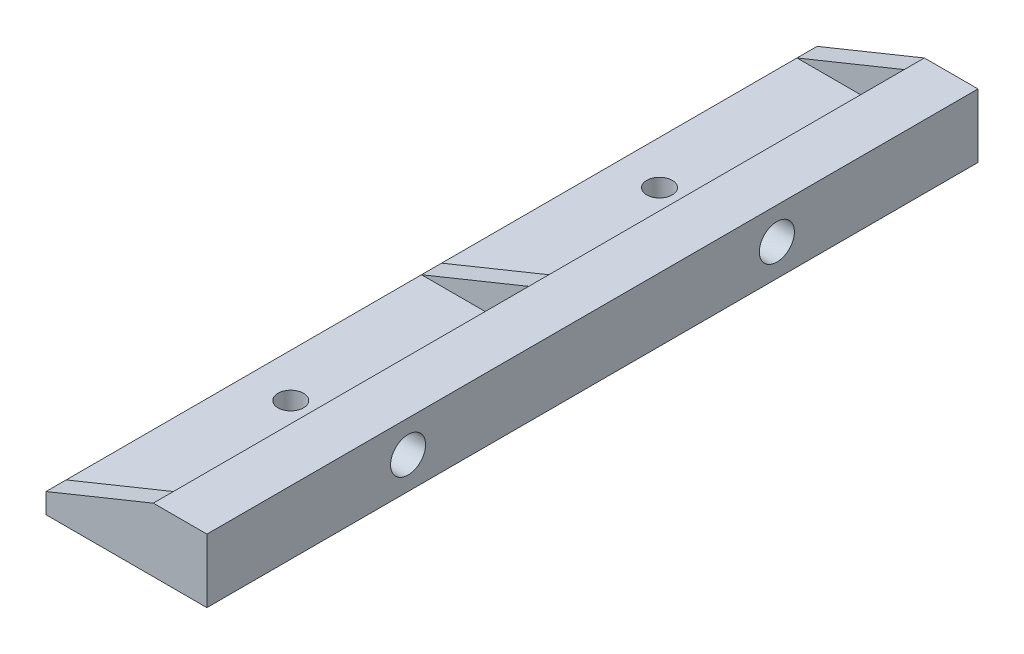
SolidWorks part; units mm, degrees
ref_plane "Front Plane" through (0, 0, 0) normal (0, 0, 1) x (1, 0, 0)
ref_plane "Top Plane" through (0, 0, 0) normal (0, 1, 0) x (1, 0, 0)
ref_plane "Right Plane" through (0, 0, 0) normal (1, 0, 0) x (0, 0, -1)
sketch "Sketch1" plane through (0, 0, 0) normal (0, 0, 1) x (1, 0, 0)
  line L0 (0, 0) -> (0, 9.5)
  line L1 (0, 9.5) -> (-8, 9.5)
  line L2 (-8, 9.5) -> (-8, 6)
  line L3 (-11, 3) -> (-24, 3)
  line L4 (-24, 3) -> (-24, 0)
  line L6 (-24, 0) -> (0, 0)
  arc A0 (-8, 6) -> (-11, 3) centre (-11, 6) cw
  dimension "D1" = 3
  dimension "D2" = 9.5
  dimension "D3" = 24
  dimension "D4" = 8
  dimension "D5" = 3
extrude "Boss-Extrude1" add sketch "Sketch1" along normal blind 115
ref_plane "Plane2" through (0, 0, 0) normal (0, 0, -1) x (-1, 0, 0)
ref_plane "Plane4" through (0, 0, 57.5) normal (0, 0, -1) x (-1, 0, 0)
sketch "Sketch4" plane through (0, 0, 57.5) normal (0, 0, -1) x (-1, 0, 0)
  line L0 (8, 9.5) -> (24, 3)
sketch "Sketch5" plane through (0, 0, 0) normal (0, 0, -1) x (-1, 0, 0)
  line L0 (8, 9.5) -> (24, 3)
rib "Rib3" sketch "Sketch4" sketch "Sketch4" thickness 3 extrusion direction parallel to sketch draft on no parameters "D1"=3
rib "Rib4" sketch "Sketch5" sketch "Sketch5" thickness 3 extrusion direction parallel to sketch draft on no parameters "D1"=3
mirror "Mirror1" about plane through (0, 0, 57.5) normal (0, 0, -1) of "Rib4"
sketch "Sketch6" plane through (0, 0, 0) normal (1, 0, 0) x (0, 0, -1)
  line L0 (-115, 4.75) -> (0, 4.75) construction
  line L1 (-115, 0) -> (-115, 9.5) construction
  line L2 (0, 0) -> (0, 9.5) construction
  circle A0 centre (-85, 4.75) radius 2.3495
  circle A1 centre (-30, 4.75) radius 2.3495
  point P6 (-85, 4.75)
  point P7 (-30, 4.75)
  dimension "D3" = 4.699
  dimension "D1" = 30
  dimension "D2" = 30
sketch "Sketch9" plane through (0, 0, 0) normal (0, -1, 0) x (1, 0, 0)
  line L0 (-17.5, 115) -> (-17.5, 0) construction
  line L1 (-24, 115) -> (0, 115) construction
  line L2 (-24, 0) -> (0, 0) construction
  line L3 (-24, 115) -> (-24, 0) construction
  point P6 (-17.5, 85)
  point P7 (-17.5, 30)
  dimension "D1" = 30
  dimension "D2" = 30
  dimension "D3" = 6.5
hole_wizard "#6 Clearance Hole1" positions "Sketch10" profile "Sketch11" hole size "#6" standard "ANSI Inch" end condition through all
sketch "Sketch10" plane through (0, 0, 0) normal (0, -1, 0) x (-1, 0, 0)
  point P0 (17.5, -30)
  point P3 (17.5, -85)
sketch "Sketch11" plane through (-17.5, 0, 30) normal (1, 0, 0) x (0, 0, -1)
  line L0 (0, 0) -> (0, 9.5)
  line L1 (0, 9.5) -> (1.8986, 9.5)
  line L2 (1.8986, 9.5) -> (1.8986, 0)
  line L5 (1.8986, 0) -> (0, 0)
  line L11 (0, -6.35) -> (0, 107.95) construction
  dimension "Thru Hole Dia." = 3.7973
  dimension "Thru Hole Depth" = 9.5
extrude "Cut-Extrude1" cut sketch "Sketch6" against normal offset from surface (7 mm away) 1 up to face at (-8, 7.75, 85.5)
sketch "Sketch12" plane through (0, 0, 0) normal (1, 0, 0) x (0, 0, -1)
  circle A0 centre (-85, 4.75) radius 2.6162
  circle A1 centre (-30, 4.75) radius 2.6162
  dimension "D1" = 5.2324
extrude "Cut-Extrude2" cut sketch "Sketch12" against normal blind 6.35
